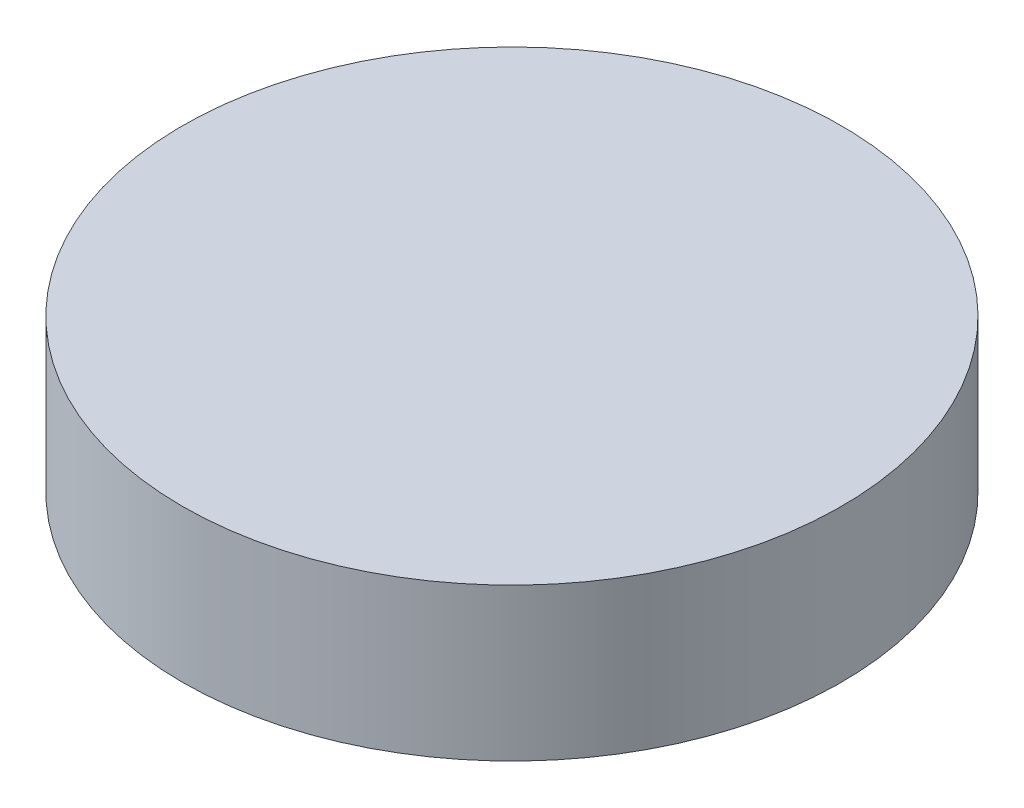
SolidWorks part; units mm, degrees
ref_plane "Front Plane" through (0, 0, 0) normal (0, 0, 1) x (1, 0, 0)
ref_plane "Top Plane" through (0, 0, 0) normal (0, 1, 0) x (1, 0, 0)
ref_plane "Right Plane" through (0, 0, 0) normal (1, 0, 0) x (0, 0, -1)
sketch "Sketch1" plane through (0, 0, 0) normal (0, 1, 0) x (1, 0, 0)
  circle A0 centre (0, 0) radius 35.433
  circle A1 centre (0, 0) radius 34.925
  dimension "D1" = 69.85
  dimension "D2" = 0.508
extrude "Boss-Extrude1" add sketch "Sketch1" along normal blind 0.508 contours A1 | A0 A1 region at (-35.3328, 0, 0) region at (0, 0, 0)
extrude "Boss-Extrude2" add sketch "Sketch1<3>" against normal blind 15.875
sketch "Sketch1<3>" plane through (0, 0, 0) normal (0, 1, 0) x (1, 0, 0) same geometry as "Sketch1"
